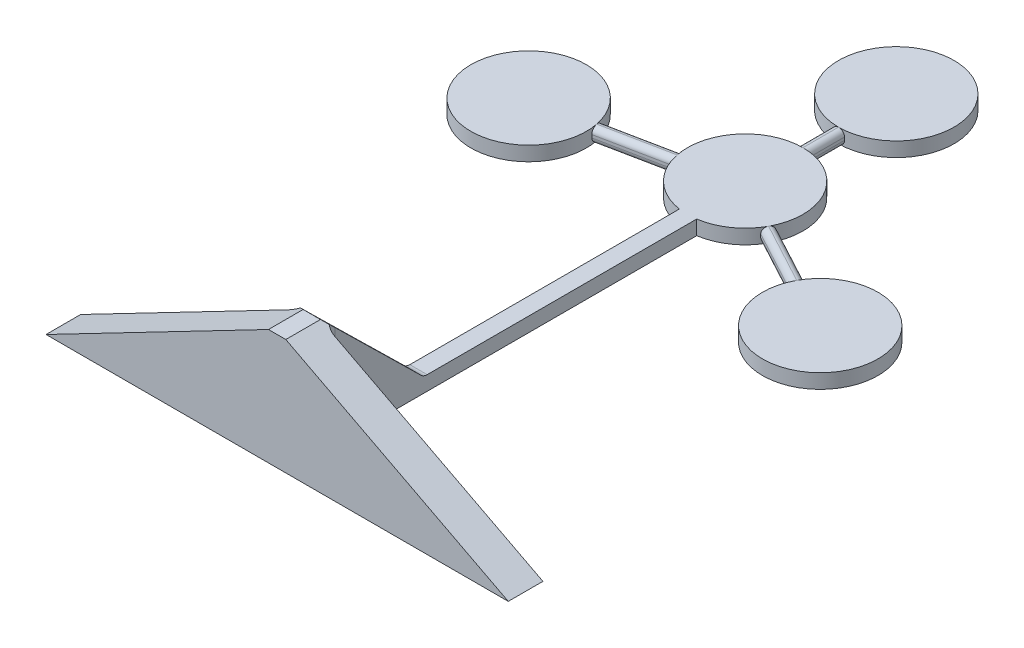
SolidWorks part; units mm, degrees
ref_plane "Front Plane" through (0, 0, 0) normal (0, 0, 1) x (1, 0, 0)
ref_plane "Top Plane" through (0, 0, 0) normal (0, 1, 0) x (1, 0, 0)
ref_plane "Right Plane" through (0, 0, 0) normal (1, 0, 0) x (0, 0, -1)
sketch "Sketch1" plane through (0, 0, 0) normal (0, 1, 0) x (1, 0, 0)
  line L0 (-62.367, -12.5813) -> (0, 0) construction
  line L22 (-80, -162) -> (80, -162)
  line L23 (-80, -162) -> (-80, -150)
  line L24 (-80, -150) -> (-3, -150)
  line L25 (80, -162) -> (80, -150)
  line L26 (0, 0) -> (56.3131, -30.3308) construction
  line L27 (0, 52.306) -> (0, 0) construction
  line L33 (3, -150) -> (80, -150)
  line L34 (-2, 32.4062) -> (-2, 19.8997)
  line L35 (-3, -19.7737) -> (-3, -150)
  line L36 (18.4685, -7.6757) -> (39.7414, -19.1335)
  line L37 (16.5717, -11.1973) -> (37.8446, -22.6551)
  line L38 (2, 32.4062) -> (2, 19.8997)
  line L39 (-19.9023, -1.9746) -> (-43.2557, -6.6857)
  line L40 (-19.1113, -5.8956) -> (-42.4647, -10.6067)
  line L41 (0, 72.306) -> (0, 128.9069) construction
  line L42 (3, -19.7737) -> (3, -150)
  line L43 (0, 0) -> (0, -175.8522) construction
  arc A0 (-19.1113, -5.8956) -> (-3, -19.7737) centre (0, 0) ccw
  arc A1 (37.8446, -22.6551) -> (39.7414, -19.1335) centre (56.3131, -30.3308) ccw
  arc A2 (-43.2557, -6.6857) -> (-42.4647, -10.6067) centre (-62.367, -12.5813) ccw
  arc A3 (2, 32.4062) -> (-2, 32.4062) centre (0, 52.306) ccw
  arc A4 (-2, 19.8997) -> (-19.9023, -1.9746) centre (0, 0) ccw
  arc A5 (18.4685, -7.6757) -> (2, 19.8997) centre (0, 0) ccw
  arc A6 (3, -19.7737) -> (16.5717, -11.1973) centre (0, 0) ccw
  dimension "D1" = 40
  dimension "D2" = 40
  dimension "D3" = 40
  dimension "D4" = 40
  dimension "D5" = 120
  dimension "D6" = 100
  dimension "D7" = 90
  dimension "D8" = 4
  dimension "D9" = 63.6233
  dimension "D10" = 52.306
  dimension "D11" = 12
  dimension "D12" = 160
  dimension "D13" = 4
  dimension "D14" = 4
  dimension "D15" = 150
  dimension "D16" = 6
extrude "Boss-Extrude1" add sketch "Sketch1" along normal blind 5
sketch "Sketch2" plane through (0, 0, 0) normal (1, 0, 0) x (0, 0, -1)
  line L0 (-150, 5) -> (-150, 40)
  line L1 (-150, 40) -> (-114.2929, 5)
  line L2 (-150, 5) -> (-19.7737, 5) construction
  line L3 (-114.2929, 5) -> (-150, 5)
  dimension "D1" = 35
  dimension "D2" = 50
extrude "Boss-Extrude2" add sketch "Sketch2" along normal mid plane 6
sketch "Sketch3" plane through (0, 5, 0) normal (0, 1, 0) x (1, 0, 0)
  line L0 (-80, -150) -> (-80, -162)
  line L1 (-80, -150) -> (80, -150)
  line L2 (-80, -162) -> (80, -162)
  line L3 (80, -150) -> (80, -162)
  point P0 (80.2506, -162)
  dimension "D1" = 12
  dimension "D2" = 160
extrude "Boss-Extrude3" add sketch "Sketch3" along normal blind 35
fillet "Fillet5" radius 3 1 edges at (0, 5, 114.2929)
sketch "Sketch4" plane through (0, 0, 150) normal (0, 0, -1) x (-1, 0, 0)
  line L0 (0, -31.8168) -> (0, 80.1056) construction
  line L1 (80, 0) -> (3, 40)
  line L2 (3, 40) -> (80, 40)
  line L3 (80, 40) -> (80, 0)
  line L4 (-80, 40) -> (-80, 0)
  line L5 (-3, 40) -> (-80, 40)
  line L6 (-80, 0) -> (-3, 40)
extrude "Cut-Extrude1" cut sketch "Sketch4" against normal through all
fillet "Fillet12" radius 5 2 edges at (3, 20, 150) (-3, 20, 150)
fillet "Fillet13" radius 2 4 edges at (-30.788, 5, 8.2512) (-30.788, 0, 8.2512) (-31.579, 5, 4.3301) (-31.579, 0, 4.3301)
fillet "Fillet14" radius 2 4 edges at (27.2081, 5, 16.9262) (29.1049, 5, 13.4046) (27.2081, 0, 16.9262) (29.1049, 0, 13.4046)
fillet "Fillet15" radius 2 4 edges at (-2, 0, -26.153) (-2, 5, -26.153) (2, 0, -26.153) (2, 5, -26.153)
